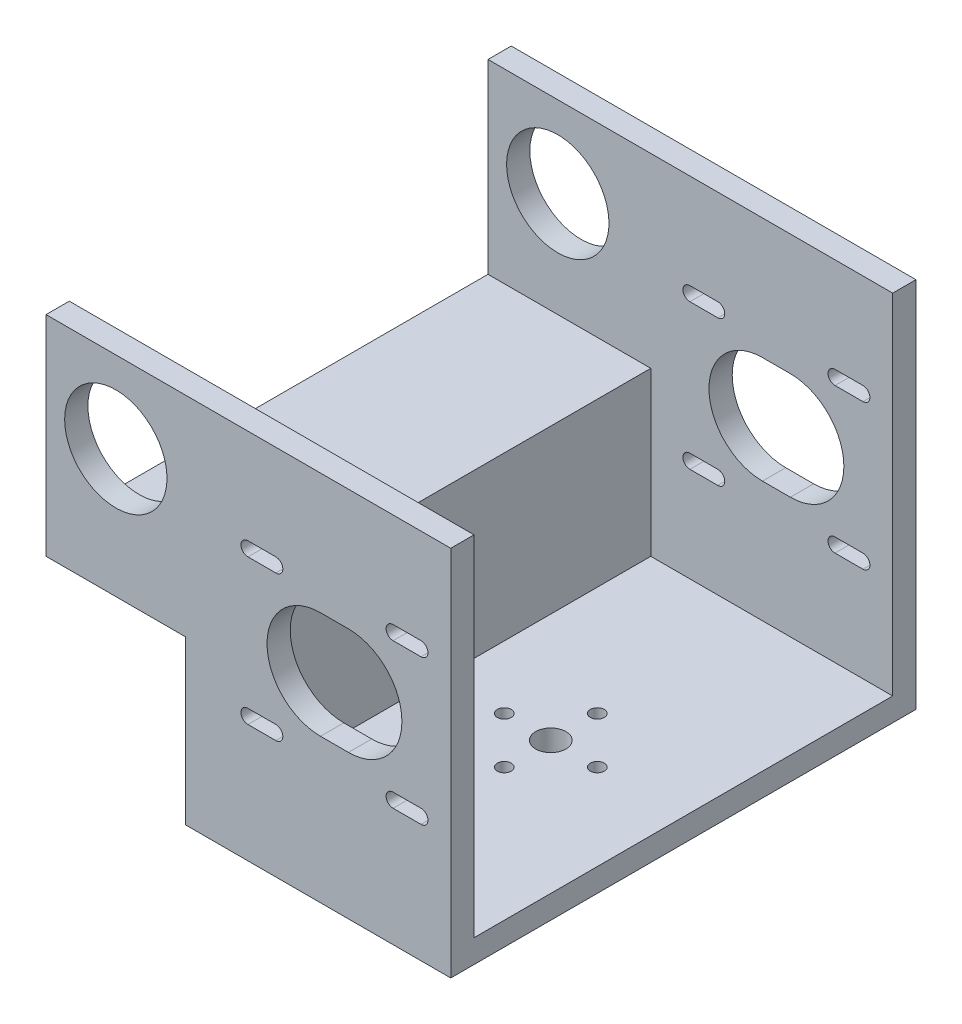
SolidWorks part; units mm, degrees
ref_plane "Front Plane" through (0, 0, 0) normal (0, 0, 1) x (1, 0, 0)
ref_plane "Top Plane" through (0, 0, 0) normal (0, 1, 0) x (1, 0, 0)
ref_plane "Right Plane" through (0, 0, 0) normal (1, 0, 0) x (0, 0, -1)
sketch "Sketch1" plane through (0, 0, 0) normal (0, 1, 0) x (1, 0, 0)
  line L1 (-28.5, 50) -> (28.5, 50)
  line L2 (-28.5, 50) -> (-28.5, -50)
  line L3 (-28.5, -50) -> (28.5, -50)
  line L4 (28.5, 50) -> (28.5, -50)
  line L5 (-28.5, 50) -> (28.5, -50) construction
  line L6 (-28.5, -50) -> (28.5, 50) construction
  point P0 (0, 0)
  dimension "D1" = 100
  dimension "D2" = 57
extrude "Boss-Extrude1" add sketch "Sketch1" along normal blind 80
sketch "Sketch3" plane through (28.5, 40, 0) normal (-1, 0, 0) x (0, 1, 0)
  line L1 (40, 45) -> (-35, 45)
  line L2 (40, 45) -> (40, -45)
  line L3 (40, -45) -> (-35, -45)
  line L4 (-35, 45) -> (-35, -45)
  line L5 (40, 45) -> (-35, -45) construction
  line L6 (40, -45) -> (-35, 45) construction
  line L10 (40, -50) -> (40, 50) construction
  line L11 (-40, -50) -> (-40, 50) construction
  line L12 (40, 50) -> (-40, 50) construction
  line L13 (40, -50) -> (-40, -50) construction
  point P0 (2.5, 0)
  dimension "D1" = 5
  dimension "D2" = 5
  dimension "D3" = 5
extrude "Cut-Extrude1" cut sketch "Sketch3" along normal blind 52
sketch "Sketch4" plane through (-40, 5, 0) normal (0, -1, 0) x (-1, 0, 0)
  line L0 (-40, 0) -> (-40, 10) construction
  circle A0 centre (-40, 0) radius 3.25
  circle A1 centre (-40, 10) radius 1.5
  circle A2 centre (-30, 0) radius 1.5
  circle A3 centre (-40, -10) radius 1.5
  circle A4 centre (-50, 0) radius 1.5
  dimension "D1" = 6.5
  dimension "D2" = 3
  dimension "D3" = 10
  dimension "D4" = 4
extrude "Cut-Extrude2" cut sketch "Sketch4" along normal through all
sketch "Sketch7" plane through (-28.5, 0, 0) normal (-1, 0, 0) x (0, 0, 1)
  line L0 (50, 80) -> (50, 0) construction
  line L1 (-50, 80) -> (-45, 80)
  line L2 (-50, 80) -> (-50, 35)
  line L4 (-45, 80) -> (-45, 40)
  line L5 (50, 80) -> (45, 80)
  line L6 (50, 80) -> (50, 35)
  line L8 (45, 80) -> (45, 40)
  line L9 (-50, 80) -> (50, 80) construction
  line L11 (-45, 40) -> (45, 40)
  line L13 (-50, 35) -> (50, 35)
  dimension "D1" = 5
  dimension "D2" = 40
  dimension "D3" = 5
extrude "Boss-Extrude2" add sketch "Sketch7" along normal blind 30
sketch "Sketch8" plane through (-28.5, 0, 0) normal (-1, 0, 0) x (0, 0, 1)
  line L4 (-45, 80) -> (-45, 40)
  line L5 (-45, 40) -> (45, 40)
  line L6 (45, 40) -> (45, 80)
  line L7 (45, 80) -> (-45, 80)
  line L8 (-45, 80) -> (-45, 40)
  line L9 (-45, 40) -> (45, 40)
  line L10 (45, 40) -> (45, 80)
  line L11 (45, 80) -> (-45, 80)
  dimension "D1" = 0
extrude "Cut-Extrude5" cut sketch "Sketch8" against normal up to next
sketch "Sketch5" plane through (0, 0, -50) normal (0, 0, -1) x (-1, 0, 0)
  line L0 (-3.5, 42.5) -> (31.0759, 42.5) construction
  line L1 (-3.5, 42.5) -> (-3.5, 17.143) construction
  line L2 (-28.5, 80) -> (58.5, 80) construction
  line L3 (-28.5, 80) -> (58.5, 80) construction
  line L4 (58.5, 80) -> (58.5, 35) construction
  line L5 (-22.1, 58.1) -> (-16.1, 58.1) construction
  line L6 (-22.1, 59.6) -> (-16.1, 59.6)
  line L7 (-22.1, 56.6) -> (-16.1, 56.6)
  line L8 (-28.5, 80) -> (-28.5, 0) construction
  line L9 (-0.5, 42.5) -> (-6.5, 42.5) construction
  line L10 (-0.5, 31) -> (-6.5, 31)
  line L11 (-0.5, 54) -> (-6.5, 54)
  line L12 (-22.1, 26.9) -> (-16.1, 26.9) construction
  line L13 (-22.1, 25.4) -> (-16.1, 25.4)
  line L14 (-22.1, 28.4) -> (-16.1, 28.4)
  line L15 (15.1, 26.9) -> (9.1, 26.9) construction
  line L16 (15.1, 25.4) -> (9.1, 25.4)
  line L17 (15.1, 28.4) -> (9.1, 28.4)
  line L18 (15.1, 58.1) -> (9.1, 58.1) construction
  line L19 (15.1, 59.6) -> (9.1, 59.6)
  line L20 (15.1, 56.6) -> (9.1, 56.6)
  circle A5 centre (43.5, 62.5) radius 11
  arc A7 (-22.1, 59.6) -> (-22.1, 56.6) centre (-22.1, 58.1) ccw
  arc A8 (-16.1, 56.6) -> (-16.1, 59.6) centre (-16.1, 58.1) ccw
  arc A9 (-0.5, 31) -> (-0.5, 54) centre (-0.5, 42.5) ccw
  arc A10 (-6.5, 54) -> (-6.5, 31) centre (-6.5, 42.5) ccw
  arc A11 (-22.1, 25.4) -> (-22.1, 28.4) centre (-22.1, 26.9) cw
  arc A12 (-16.1, 28.4) -> (-16.1, 25.4) centre (-16.1, 26.9) cw
  arc A13 (15.1, 25.4) -> (15.1, 28.4) centre (15.1, 26.9) ccw
  arc A14 (9.1, 28.4) -> (9.1, 25.4) centre (9.1, 26.9) ccw
  arc A15 (15.1, 59.6) -> (15.1, 56.6) centre (15.1, 58.1) cw
  arc A16 (9.1, 56.6) -> (9.1, 59.6) centre (9.1, 58.1) cw
  point P2 (-19.1, 58.1)
  point P8 (-19.1, 42.5)
  point P13 (-3.5, 42.5)
  point P31 (-19.1, 26.9)
  point P38 (12.1, 26.9)
  point P45 (12.1, 58.1)
  dimension "D5" = 15.6
  dimension "D8" = 6
  dimension "D9" = 22
  dimension "D2" = 1.5
  dimension "D7" = 11.5
  dimension "D12" = 25
  dimension "D3" = 15.6
  dimension "D4" = 6
  dimension "D6" = 37.5
  dimension "D10" = 17.5
  dimension "D11" = 15
extrude "Cut-Extrude3" cut sketch "Sketch5" against normal through all
